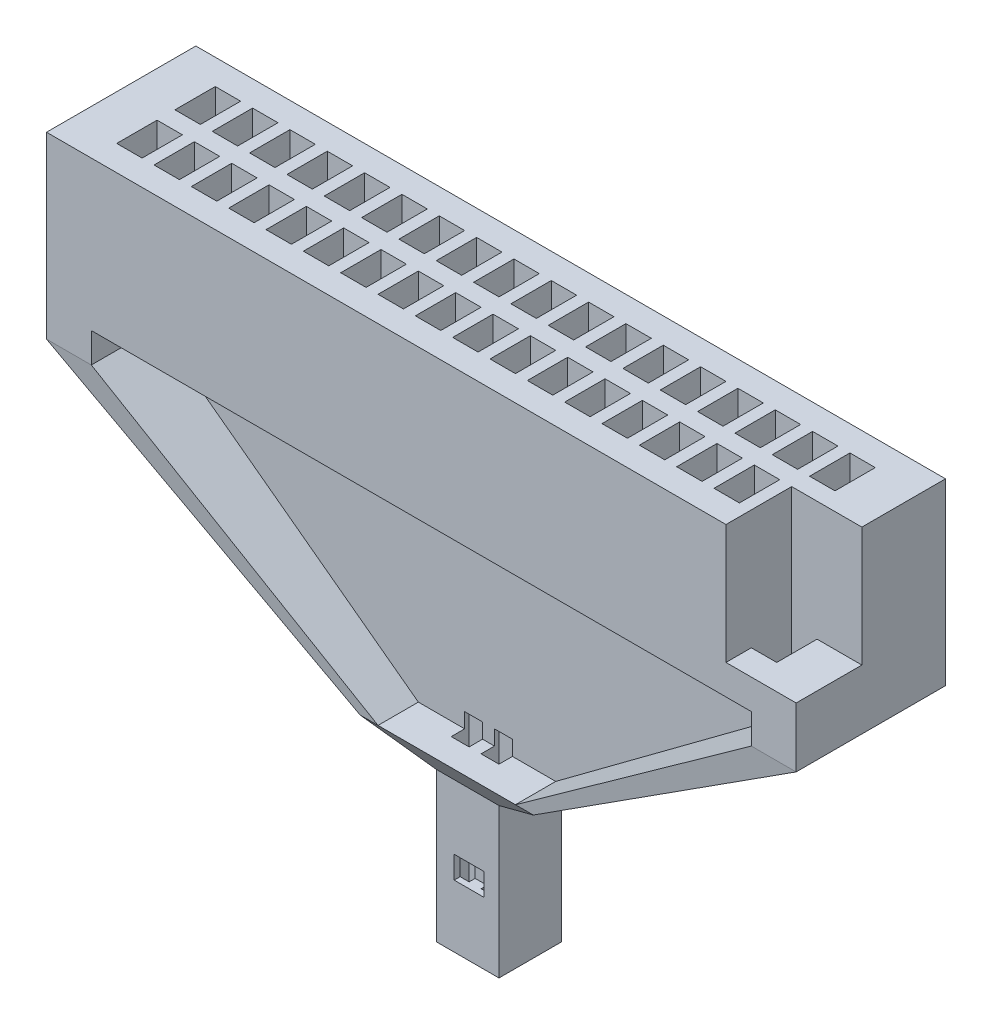
SolidWorks part; units mm, degrees
note: The reader was unsure of these and kept them because the rebuilt part matched: shared geometry of "Sketch13<3>".
ref_plane "Front Plane" through (0, 0, 0) normal (0, 0, 1) x (1, 0, 0)
ref_plane "Top Plane" through (0, 0, 0) normal (0, 1, 0) x (1, 0, 0)
ref_plane "Right Plane" through (0, 0, 0) normal (1, 0, 0) x (0, 0, -1)
sketch "main_block" plane through (0, 0, 0) normal (0, 1, 0) x (1, 0, 0)
  line L1 (-5.6188, 1.2192) -> (7.132, 1.2192)
  line L2 (-5.6188, 1.2192) -> (-5.6188, -1.3208)
  line L3 (-5.6188, -1.3208) -> (7.132, -1.3208)
  line L4 (7.132, 1.2192) -> (7.132, -1.3208)
  dimension "D1" = 12.7508
  dimension "D2" = 2.54
sketch "top_holes" plane through (0, 0, 0) normal (0, 1, 0) x (1, 0, 0)
  line L0 (7.132, 1.2192) -> (7.132, -1.3208) construction
  line L1 (6.37, 0.7874) -> (5.9382, 0.7874)
  line L2 (6.37, 0.7874) -> (6.37, 0.1016)
  line L3 (6.37, 0.1016) -> (5.9382, 0.1016)
  line L4 (5.9382, 0.7874) -> (5.9382, 0.1016)
  line L5 (-5.6188, 1.2192) -> (7.132, 1.2192) construction
  line L6 (5.3032, 0.7874) -> (5.3032, 0.1016)
  line L7 (5.735, 0.7874) -> (5.3032, 0.7874)
  line L8 (5.735, 0.7874) -> (5.735, 0.1016)
  line L9 (5.735, 0.1016) -> (5.3032, 0.1016)
  line L10 (4.6682, 0.7874) -> (4.6682, 0.1016)
  line L11 (5.1, 0.7874) -> (4.6682, 0.7874)
  line L12 (5.1, 0.7874) -> (5.1, 0.1016)
  line L13 (5.1, 0.1016) -> (4.6682, 0.1016)
  line L14 (4.0332, 0.7874) -> (4.0332, 0.1016)
  line L15 (4.465, 0.7874) -> (4.0332, 0.7874)
  line L16 (4.465, 0.7874) -> (4.465, 0.1016)
  line L17 (4.465, 0.1016) -> (4.0332, 0.1016)
  line L18 (3.3982, 0.7874) -> (3.3982, 0.1016)
  line L19 (3.83, 0.7874) -> (3.3982, 0.7874)
  line L20 (3.83, 0.7874) -> (3.83, 0.1016)
  line L21 (3.83, 0.1016) -> (3.3982, 0.1016)
  line L22 (2.7632, 0.7874) -> (2.7632, 0.1016)
  line L23 (3.195, 0.7874) -> (2.7632, 0.7874)
  line L24 (3.195, 0.7874) -> (3.195, 0.1016)
  line L25 (3.195, 0.1016) -> (2.7632, 0.1016)
  line L26 (2.1282, 0.7874) -> (2.1282, 0.1016)
  line L27 (2.56, 0.7874) -> (2.1282, 0.7874)
  line L28 (2.56, 0.7874) -> (2.56, 0.1016)
  line L29 (2.56, 0.1016) -> (2.1282, 0.1016)
  line L30 (1.4932, 0.7874) -> (1.4932, 0.1016)
  line L31 (1.925, 0.7874) -> (1.4932, 0.7874)
  line L32 (1.925, 0.7874) -> (1.925, 0.1016)
  line L33 (1.925, 0.1016) -> (1.4932, 0.1016)
  line L34 (0.8582, 0.7874) -> (0.8582, 0.1016)
  line L35 (1.29, 0.7874) -> (0.8582, 0.7874)
  line L36 (1.29, 0.7874) -> (1.29, 0.1016)
  line L37 (1.29, 0.1016) -> (0.8582, 0.1016)
  line L38 (0.2232, 0.7874) -> (0.2232, 0.1016)
  line L39 (0.655, 0.7874) -> (0.2232, 0.7874)
  line L40 (0.655, 0.7874) -> (0.655, 0.1016)
  line L41 (0.655, 0.1016) -> (0.2232, 0.1016)
  line L42 (-0.4117, 0.7874) -> (-0.4117, 0.1016)
  line L43 (0.0201, 0.7874) -> (-0.4117, 0.7874)
  line L44 (0.0201, 0.7874) -> (0.0201, 0.1016)
  line L45 (0.0201, 0.1016) -> (-0.4117, 0.1016)
  line L46 (-1.0467, 0.7874) -> (-1.0467, 0.1016)
  line L47 (-0.6149, 0.7874) -> (-1.0467, 0.7874)
  line L48 (-0.6149, 0.7874) -> (-0.6149, 0.1016)
  line L49 (-0.6149, 0.1016) -> (-1.0467, 0.1016)
  line L50 (-1.6817, 0.7874) -> (-1.6817, 0.1016)
  line L51 (-1.2499, 0.7874) -> (-1.6817, 0.7874)
  line L52 (-1.2499, 0.7874) -> (-1.2499, 0.1016)
  line L53 (-1.2499, 0.1016) -> (-1.6817, 0.1016)
  line L54 (-2.3167, 0.7874) -> (-2.3167, 0.1016)
  line L55 (-1.8849, 0.7874) -> (-2.3167, 0.7874)
  line L56 (-1.8849, 0.7874) -> (-1.8849, 0.1016)
  line L57 (-1.8849, 0.1016) -> (-2.3167, 0.1016)
  line L58 (-2.9517, 0.7874) -> (-2.9517, 0.1016)
  line L59 (-2.5199, 0.7874) -> (-2.9517, 0.7874)
  line L60 (-2.5199, 0.7874) -> (-2.5199, 0.1016)
  line L61 (-2.5199, 0.1016) -> (-2.9517, 0.1016)
  line L62 (-3.5867, 0.7874) -> (-3.5867, 0.1016)
  line L63 (-3.1549, 0.7874) -> (-3.5867, 0.7874)
  line L64 (-3.1549, 0.7874) -> (-3.1549, 0.1016)
  line L65 (-3.1549, 0.1016) -> (-3.5867, 0.1016)
  line L66 (-4.2217, 0.7874) -> (-4.2217, 0.1016)
  line L67 (-3.7899, 0.7874) -> (-4.2217, 0.7874)
  line L68 (-3.7899, 0.7874) -> (-3.7899, 0.1016)
  line L69 (-3.7899, 0.1016) -> (-4.2217, 0.1016)
  line L70 (-4.8567, 0.7874) -> (-4.8567, 0.1016)
  line L71 (-4.4249, 0.7874) -> (-4.8567, 0.7874)
  line L72 (-4.4249, 0.7874) -> (-4.4249, 0.1016)
  line L73 (-4.4249, 0.1016) -> (-4.8567, 0.1016)
  line L74 (5.3032, -0.2032) -> (5.3032, -0.889)
  line L75 (5.735, -0.2032) -> (5.3032, -0.2032)
  line L76 (5.735, -0.2032) -> (5.735, -0.889)
  line L77 (5.735, -0.889) -> (5.3032, -0.889)
  line L78 (4.6682, -0.2032) -> (4.6682, -0.889)
  line L79 (5.1, -0.2032) -> (4.6682, -0.2032)
  line L80 (5.1, -0.2032) -> (5.1, -0.889)
  line L81 (5.1, -0.889) -> (4.6682, -0.889)
  line L82 (4.0332, -0.2032) -> (4.0332, -0.889)
  line L83 (4.465, -0.2032) -> (4.0332, -0.2032)
  line L84 (4.465, -0.2032) -> (4.465, -0.889)
  line L85 (4.465, -0.889) -> (4.0332, -0.889)
  line L86 (3.3982, -0.2032) -> (3.3982, -0.889)
  line L87 (3.83, -0.2032) -> (3.3982, -0.2032)
  line L88 (3.83, -0.2032) -> (3.83, -0.889)
  line L89 (3.83, -0.889) -> (3.3982, -0.889)
  line L90 (2.7632, -0.2032) -> (2.7632, -0.889)
  line L91 (3.195, -0.2032) -> (2.7632, -0.2032)
  line L92 (3.195, -0.2032) -> (3.195, -0.889)
  line L93 (3.195, -0.889) -> (2.7632, -0.889)
  line L94 (2.1282, -0.2032) -> (2.1282, -0.889)
  line L95 (2.56, -0.2032) -> (2.1282, -0.2032)
  line L96 (2.56, -0.2032) -> (2.56, -0.889)
  line L97 (2.56, -0.889) -> (2.1282, -0.889)
  line L98 (1.4932, -0.2032) -> (1.4932, -0.889)
  line L99 (1.925, -0.2032) -> (1.4932, -0.2032)
  line L100 (1.925, -0.2032) -> (1.925, -0.889)
  line L101 (1.925, -0.889) -> (1.4932, -0.889)
  line L102 (0.8582, -0.2032) -> (0.8582, -0.889)
  line L103 (1.29, -0.2032) -> (0.8582, -0.2032)
  line L104 (1.29, -0.2032) -> (1.29, -0.889)
  line L105 (1.29, -0.889) -> (0.8582, -0.889)
  line L106 (0.2232, -0.2032) -> (0.2232, -0.889)
  line L107 (0.655, -0.2032) -> (0.2232, -0.2032)
  line L108 (0.655, -0.2032) -> (0.655, -0.889)
  line L109 (0.655, -0.889) -> (0.2232, -0.889)
  line L110 (-0.4117, -0.2032) -> (-0.4117, -0.889)
  line L111 (0.0201, -0.2032) -> (-0.4117, -0.2032)
  line L112 (0.0201, -0.2032) -> (0.0201, -0.889)
  line L113 (0.0201, -0.889) -> (-0.4117, -0.889)
  line L114 (-1.0467, -0.2032) -> (-1.0467, -0.889)
  line L115 (-0.6149, -0.2032) -> (-1.0467, -0.2032)
  line L116 (-0.6149, -0.2032) -> (-0.6149, -0.889)
  line L117 (-0.6149, -0.889) -> (-1.0467, -0.889)
  line L118 (-1.6817, -0.2032) -> (-1.6817, -0.889)
  line L119 (-1.2499, -0.2032) -> (-1.6817, -0.2032)
  line L120 (-1.2499, -0.2032) -> (-1.2499, -0.889)
  line L121 (-1.2499, -0.889) -> (-1.6817, -0.889)
  line L122 (-2.3167, -0.2032) -> (-2.3167, -0.889)
  line L123 (-1.8849, -0.2032) -> (-2.3167, -0.2032)
  line L124 (-1.8849, -0.2032) -> (-1.8849, -0.889)
  line L125 (-1.8849, -0.889) -> (-2.3167, -0.889)
  line L126 (-2.9517, -0.2032) -> (-2.9517, -0.889)
  line L127 (-2.5199, -0.2032) -> (-2.9517, -0.2032)
  line L128 (-2.5199, -0.2032) -> (-2.5199, -0.889)
  line L129 (-2.5199, -0.889) -> (-2.9517, -0.889)
  line L130 (-3.5867, -0.2032) -> (-3.5867, -0.889)
  line L131 (-3.1549, -0.2032) -> (-3.5867, -0.2032)
  line L132 (-3.1549, -0.2032) -> (-3.1549, -0.889)
  line L133 (-3.1549, -0.889) -> (-3.5867, -0.889)
  line L134 (-4.2217, -0.2032) -> (-4.2217, -0.889)
  line L135 (-3.7899, -0.2032) -> (-4.2217, -0.2032)
  line L136 (-3.7899, -0.2032) -> (-3.7899, -0.889)
  line L137 (-3.7899, -0.889) -> (-4.2217, -0.889)
  line L138 (-4.8567, -0.2032) -> (-4.8567, -0.889)
  line L139 (-4.4249, -0.2032) -> (-4.8567, -0.2032)
  line L140 (-4.4249, -0.2032) -> (-4.4249, -0.889)
  line L141 (-4.4249, -0.889) -> (-4.8567, -0.889)
  line L142 (5.9382, -0.2032) -> (5.9382, -0.889)
  line L143 (6.37, -0.2032) -> (5.9382, -0.2032)
  line L144 (6.37, -0.2032) -> (6.37, -0.889)
  line L145 (6.37, -0.889) -> (5.9382, -0.889)
  line L148 (-5.6188, 1.2192) -> (-5.6188, -1.3208) construction
  dimension "D1" = 0.4318
  dimension "D2" = 0.6858
  dimension "D3" = 0.762
  dimension "D4" = 0.4318
  dimension "D5" = 18
  dimension "D6" = 2
extrude "Boss-Extrude1" add sketch "main_block" against normal blind 2.54
extrude "Cut-Extrude1" cut sketch "top_holes" against normal blind 2.54
ref_plane "Plane1" through (0, -6.35, 0) normal (0, 1, 0) x (1, 0, 0)
sketch "Sketch4" plane through (0, -6.35, 0) normal (0, 1, 0) x (1, 0, 0)
  line L1 (1.9249, 0.889) -> (-0.4117, 0.889)
  line L2 (1.9249, 0.889) -> (1.9249, -0.889)
  line L3 (1.9249, -0.889) -> (-0.4117, -0.889)
  line L4 (-0.4117, 0.889) -> (-0.4117, -0.889)
  line L5 (1.9249, 0.889) -> (-0.4117, -0.889) construction
  line L6 (1.9249, -0.889) -> (-0.4117, 0.889) construction
  point P0 (0.7566, 0)
  dimension "D1" = 2.3367
  dimension "D2" = 1.778
sketch "Sketch5" plane through (0, -2.54, 0) normal (0, -1, 0) x (1, 0, 0)
  line L1 (-4.8567, 0.2032) -> (6.37, 0.2032)
  line L2 (-4.8567, 0.2032) -> (-4.8567, -0.1016)
  line L3 (-4.8567, -0.1016) -> (6.37, -0.1016)
  line L4 (6.37, 0.2032) -> (6.37, -0.1016)
sketch "Sketch6" plane through (0, -6.35, 0) normal (0, 1, 0) x (1, 0, 0)
  line L1 (-0.4117, 0.1016) -> (1.925, 0.1016)
  line L2 (-0.4117, 0.1016) -> (-0.4117, -0.2032)
  line L3 (-0.4117, -0.2032) -> (1.925, -0.2032)
  line L4 (1.925, 0.1016) -> (1.925, -0.2032)
sketch "Sketch7" plane through (0, -6.35, 0) normal (0, 1, 0) x (1, 0, 0)
  line L0 (-0.4117, -0.889) -> (-0.4117, 0.889)
  line L1 (-0.4117, -0.889) -> (-0.7165, -0.889)
  line L2 (-0.4117, 0.889) -> (-0.7165, 0.889)
  line L3 (-0.7165, -0.889) -> (-0.7165, 0.889)
  dimension "D1" = 0.3048
sketch "Sketch8" plane through (0, -2.54, 0) normal (0, -1, 0) x (1, 0, 0)
  line L0 (-4.8567, 1.3208) -> (-4.8567, -1.2192)
  line L1 (-4.8567, 1.3208) -> (-5.6187, 1.3208)
  line L2 (-4.8567, -1.2192) -> (-5.6187, -1.2192)
  line L3 (-5.6187, 1.3208) -> (-5.6187, -1.2192)
  line L4 (-5.6188, 1.3208) -> (7.132, 1.3208) construction
  line L5 (7.132, -1.2192) -> (-5.6188, -1.2192) construction
  dimension "D1" = 0.762
  dimension "D2" = 0
  dimension "D3" = 0
extrude "Boss-Extrude3" add sketch "Sketch8" along normal blind 0.508
sketch "Sketch9" plane through (0, -6.35, 0) normal (0, 1, 0) x (1, 0, 0)
  line L0 (1.925, -0.889) -> (1.9249, 0.889)
  line L1 (1.925, -0.889) -> (2.2298, -0.889)
  line L2 (1.9249, 0.889) -> (2.2297, 0.889)
  line L3 (2.2298, -0.889) -> (2.2297, 0.889)
  dimension "D1" = 0.3048
sketch "Sketch10" plane through (0, -2.54, 0) normal (0, -1, 0) x (1, 0, 0)
  line L0 (6.37, -1.2192) -> (6.37, 1.3208)
  line L1 (6.37, -1.2192) -> (7.132, -1.2192)
  line L2 (6.37, 1.3208) -> (7.132, 1.3208)
  line L3 (7.132, -1.2192) -> (7.132, 1.3208)
  line L4 (-5.6188, 1.3208) -> (-5.6187, 1.3208) construction
  line L5 (7.132, -1.2192) -> (-4.8567, -1.2192) construction
  dimension "D1" = 0.762
  dimension "D2" = 0
  dimension "D3" = 0
extrude "Boss-Extrude2" add sketch "Sketch10" along normal blind 0.508
loft "Loft4" add profiles "Sketch9" section "Sketch9" section face at (6.751, -3.048, 0.0508) connector at (1.925, -6.35, 0.889) connector at (6.37, -3.048, 1.3208)
loft "Loft14" add profiles "Sketch7" section "Sketch7" section face at (-5.2377, -3.048, 0.0508) connector at (-0.4117, -6.35, 0.889) connector at (-4.8567, -3.048, 1.3208)
extrude "Boss-Extrude5" add sketch "Sketch5" along normal blind 0.508
loft "Loft15" add profiles "Sketch6" section face at (0.7566, -3.048, 0.0508) section "Sketch6" connector at (-4.8567, -3.048, -0.1016) connector at (-0.4117, -6.35, -0.1016)
sketch "Sketch12" plane through (0, -6.35, 0) normal (0, 1, 0) x (1, 0, 0)
  line L1 (-0.7165, 0.889) -> (2.2299, 0.889)
  line L2 (-0.7165, 0.889) -> (-0.7165, -0.889)
  line L3 (-0.7165, -0.889) -> (2.2299, -0.889)
  line L4 (2.2299, 0.889) -> (2.2299, -0.889)
  line L6 (-0.4117, 0.889) -> (-0.7165, 0.889) construction
  line L7 (-0.7165, -0.889) -> (-0.4117, -0.889) construction
  dimension "D1" = 0
  dimension "D2" = 2.9464
  dimension "D3" = 0
ref_plane "Plane2" through (0, -6.858, 0) normal (0, 1, 0) x (1, 0, 0)
sketch "Sketch13" plane through (0, -6.858, 0) normal (0, 1, 0) x (1, 0, 0)
  line L1 (1.29, 0.5334) -> (0.2232, 0.5334)
  line L2 (1.29, 0.5334) -> (1.29, -0.5334)
  line L3 (1.29, -0.5334) -> (0.2232, -0.5334)
  line L4 (0.2232, 0.5334) -> (0.2232, -0.5334)
  line L5 (1.29, 0.5334) -> (0.2232, -0.5334) construction
  line L6 (1.29, -0.5334) -> (0.2232, 0.5334) construction
  point P0 (0.7566, 0)
  dimension "D1" = 1.0668
  dimension "D2" = 1.0668
loft "Loft16" add profiles "Sketch12", "Sketch13" connector at (2.2299, -6.35, -0.889) connector at (1.29, -6.858, -0.5334)
extrude "Boss-Extrude6" add sketch "Sketch13<3>" against normal blind 2.54
sketch "Sketch13<3>" plane through (0, -6.858, 0) normal (0, 1, 0) x (1, 0, 0) same geometry as "Sketch13"
sketch "Sketch14" plane through (0, -9.398, 0) normal (0, -1, 0) x (1, 0, 0)
  line L0 (1.29, -0.5334) -> (0.2232, -0.5334) construction
  line L1 (0.3756, -0.381) -> (0.6804, -0.381)
  line L2 (0.3756, -0.381) -> (0.3756, -0.0762)
  line L3 (0.3756, -0.0762) -> (0.6804, -0.0762)
  line L4 (0.6804, -0.381) -> (0.6804, -0.0762)
  line L5 (0.2232, -0.5334) -> (0.2232, 0.5334) construction
  line L6 (0.8836, -0.0762) -> (1.1884, -0.0762)
  line L7 (1.1884, -0.381) -> (1.1884, -0.0762)
  line L8 (0.8836, -0.381) -> (1.1884, -0.381)
  line L9 (0.8836, -0.381) -> (0.8836, -0.0762)
  line L10 (0.8836, 0.4318) -> (1.1884, 0.4318)
  line L11 (1.1884, 0.127) -> (1.1884, 0.4318)
  line L12 (0.8836, 0.127) -> (1.1884, 0.127)
  line L13 (0.8836, 0.127) -> (0.8836, 0.4318)
  line L14 (0.3756, 0.4318) -> (0.6804, 0.4318)
  line L15 (0.6804, 0.127) -> (0.6804, 0.4318)
  line L16 (0.3756, 0.127) -> (0.6804, 0.127)
  line L17 (0.3756, 0.127) -> (0.3756, 0.4318)
  dimension "D1" = 0.3048
  dimension "D2" = 0.3048
  dimension "D3" = 0.1524
  dimension "D4" = 0.1524
  dimension "D5" = 2
  dimension "D6" = 2
extrude "Cut-Extrude2" cut sketch "Sketch14" against normal blind 3.302
sketch "Sketch15" plane through (0, 0, 0.5334) normal (0, 0, 1) x (1, 0, 0)
  line L0 (0.6804, -6.35) -> (0.6804, -9.398) construction
  line L1 (0.528, -8.3373) -> (1.036, -8.3373)
  line L2 (0.528, -8.3373) -> (0.528, -7.9563)
  line L3 (0.528, -7.9563) -> (1.036, -7.9563)
  line L4 (1.036, -8.3373) -> (1.036, -7.9563)
  line L5 (0.8836, -6.35) -> (0.8836, -9.398) construction
  dimension "D1" = 0.1524
  dimension "D2" = 0.1524
  dimension "D3" = 0.381
extrude "Cut-Extrude3" cut sketch "Sketch15" against normal blind 0.2032
sketch "Sketch16" plane through (0, 0, -0.5334) normal (0, 0, -1) x (-1, 0, 0)
  line L1 (-1.036, -8.3373) -> (-0.528, -8.3373)
  line L2 (-1.036, -8.3373) -> (-1.036, -7.9563)
  line L3 (-1.036, -7.9563) -> (-0.528, -7.9563)
  line L4 (-0.528, -8.3373) -> (-0.528, -7.9563)
extrude "Cut-Extrude4" cut sketch "Sketch16" against normal blind 0.2032
sketch "Sketch17" plane through (0, 0, 0) normal (0, 1, 0) x (1, 0, 0)
  line L1 (5.9382, -0.2032) -> (7.132, -0.2032)
  line L2 (5.9382, -0.2032) -> (5.9382, -1.3208)
  line L3 (5.9382, -1.3208) -> (7.132, -1.3208)
  line L4 (7.132, -0.2032) -> (7.132, -1.3208)
extrude "Cut-Extrude5" cut sketch "Sketch17" against normal blind 2.032
